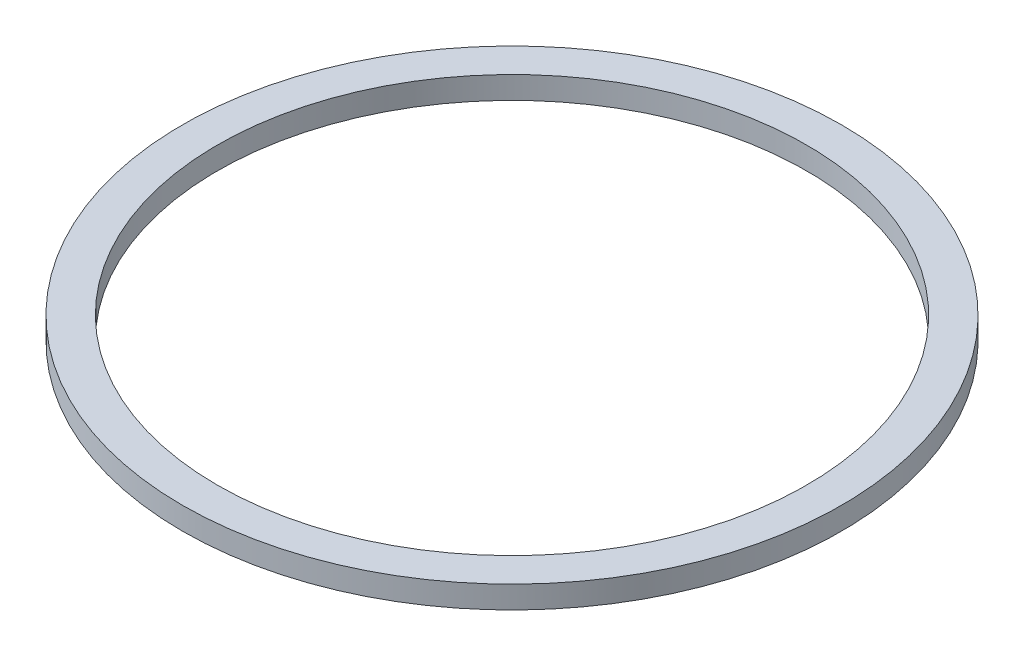
SolidWorks part; units mm, degrees
ref_plane "Front Plane" through (0, 0, 0) normal (0, 0, 1) x (1, 0, 0)
ref_plane "Top Plane" through (0, 0, 0) normal (0, 1, 0) x (1, 0, 0)
ref_plane "Right Plane" through (0, 0, 0) normal (1, 0, 0) x (0, 0, -1)
sketch "Sketch1" plane through (0, 0, 0) normal (0, 1, 0) x (1, 0, 0)
  circle A0 centre (0, 0) radius 125
  circle A1 centre (0, 0) radius 111.75
  dimension "D1" = 250
  dimension "D2" = 223.5
extrude "Boss-Extrude1" add sketch "Sketch1" along normal blind 8.5
